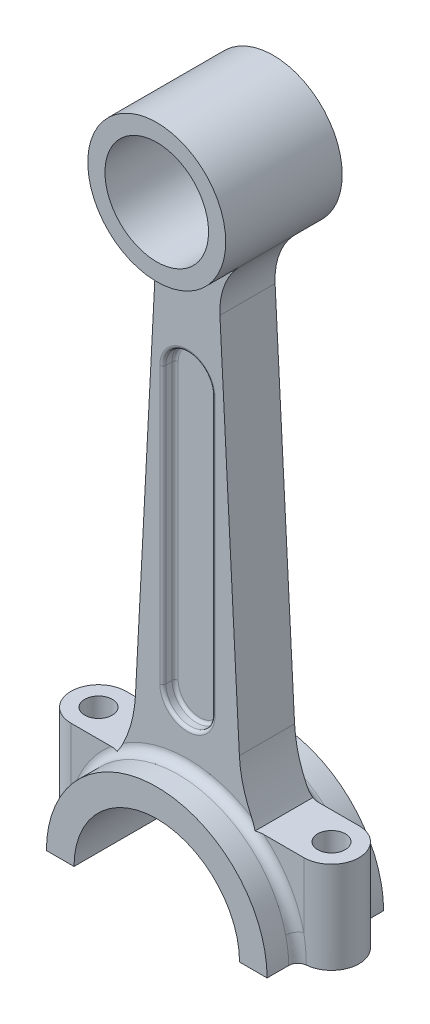
SolidWorks part; units mm, degrees
ref_plane "Ön Düzlem" through (0, 0, 0) normal (0, 0, 1) x (1, 0, 0)
ref_plane "Üst Düzlem" through (0, 0, 0) normal (0, 1, 0) x (1, 0, 0)
ref_plane "Sağ Düzlem" through (0, 0, 0) normal (1, 0, 0) x (0, 0, -1)
sketch "Çizim1" plane through (0, 0, 0) normal (0, 0, 1) x (1, 0, 0)
  line L0 (0, -201.2) -> (0, 0) construction
  line L1 (-10, -20.1556) -> (-17.8497, -169.9368)
  line L2 (10, -20.1556) -> (17.8497, -169.9368)
  line L3 (-36, -201.2) -> (-27, -201.2)
  line L4 (27, -201.2) -> (36, -201.2)
  circle A0 centre (0, 0) radius 16.9
  circle A1 centre (0, 0) radius 22.5
  arc A2 (27, -201.2) -> (-27, -201.2) centre (0, -201.2) ccw
  arc A3 (36, -201.2) -> (-36, -201.2) centre (0, -201.2) ccw
  dimension "D1" = 33.8
  dimension "D2" = 45
  dimension "D3" = 54
  dimension "D4" = 72
  dimension "D5" = 201.2
  dimension "D6" = 20
  dimension "D7" = 6
extrude "Yükseklik-Ekstrüzyon1" add sketch "Çizim1" along normal mid plane 38 contours A1 A0 | A2 A3 | L3 A2 L4 A3 region at (-11.5231, 18.5805, 0) region at (0, -166.005, 0)
extrude "Yükseklik-Ekstrüzyon2" add sketch "Çizim1<3>" along normal mid plane 18 contours L0 A3 L2 A1 | A3 L0 A1 L1 region at (-7.1843, -100.8455, 0) region at (7.1843, -100.8455, 0)
sketch "Çizim1<3>" plane through (0, 0, 0) normal (0, 0, 1) x (1, 0, 0) same geometry as "Çizim1"
sketch "Çizim2" plane through (0, 0, 9) normal (0, 0, 1) x (1, 0, 0)
  line L0 (0, 0) -> (0, -201.2) construction
  line L1 (0, -145.6) -> (0, -55.6) construction
  line L2 (-8, -145.6) -> (-8, -55.6)
  line L3 (8, -145.6) -> (8, -55.6)
  arc A0 (-8, -145.6) -> (8, -145.6) centre (0, -145.6) ccw
  arc A1 (8, -55.6) -> (-8, -55.6) centre (0, -55.6) ccw
  point P6 (0, -100.6)
  dimension "D1" = 8
  dimension "D2" = 90
extrude "Kes-Ekstrüzyon1" cut sketch "Çizim2" against normal blind 4
mirror "Aynalama1" about plane through (0, 0, 0) normal (0, 0, 1) of "Kes-Ekstrüzyon1"
fillet "Radyus1" radius 1 16 edges at (0, -153.6, -5) (-8, -100.6, -5) (0, -47.6, -5) (0, -153.6, -9) (-8, -100.6, -9) (0, -47.6, -9) (0, -153.6, 5) (-8, -100.6, 5) (0, -47.6, 5) (0, -47.6, 9) (8, -100.6, 9) (0, -153.6, 9) (8, -100.6, -5) (8, -100.6, -9) (8, -100.6, 5) (-8, -100.6, 9)
ref_plane "Düzlem1" through (0, -171.2, 0) normal (0, -1, 0) x (-1, 0, 0)
fillet "Radyus2" radius 40 2 edges at (17.8497, -169.9368, 0) (-17.8497, -169.9368, 0)
fillet "Radyus3" radius 22.5 2 edges at (10, -20.1556, 0) (-10, -20.1556, 0)
sketch "Çizim3" plane through (0, -171.2, 0) normal (0, -1, 0) x (-1, 0, 0)
  line L0 (38, 0) -> (-38, 0) construction
  line L1 (38, -9) -> (-38, -9)
  line L2 (38, 9) -> (-38, 9)
  arc A0 (38, -9) -> (38, 9) centre (38, 0) ccw
  arc A1 (-38, 9) -> (-38, -9) centre (-38, 0) ccw
  point P2 (0, 0)
  dimension "D2" = 9
  dimension "D1" = 76
extrude "Yükseklik-Ekstrüzyon3" add sketch "Çizim3" along normal up to surface (30 mm away) up to face at (31.5, -201.2, 0)
sketch "Çizim5" plane through (0, 0, -9) normal (0, 0, -1) x (-1, 0, 0)
  line L1 (-27, -201.2) -> (27, -201.2)
  line L2 (-27, -201.2) -> (27, -201.2)
  arc A1 (27, -201.2) -> (-27, -201.2) centre (0, -201.2) ccw
  arc A2 (27, -201.2) -> (-27, -201.2) centre (0, -201.2) ccw
  dimension "D1" = 0
extrude "Kes-Ekstrüzyon2" cut sketch "Çizim5" against normal blind 68
sketch "Çizim6" plane through (0, -171.2, 0) normal (0, 1, 0) x (1, 0, 0)
  line L0 (-19.8997, -9) -> (-19.8997, 9) construction
  line L2 (-22.4835, -9) -> (-38, -9) construction
  circle A0 centre (-38, 0) radius 4.5
  circle A1 centre (38, 0) radius 4.5
  dimension "D1" = 9
  dimension "D3" = 57.8997
extrude "Kes-Ekstrüzyon3" cut sketch "Çizim6" against normal blind 68
fillet "Radyus4" radius 3 2 edges at (0, -165.2, -9) (0, -165.2, 9)
